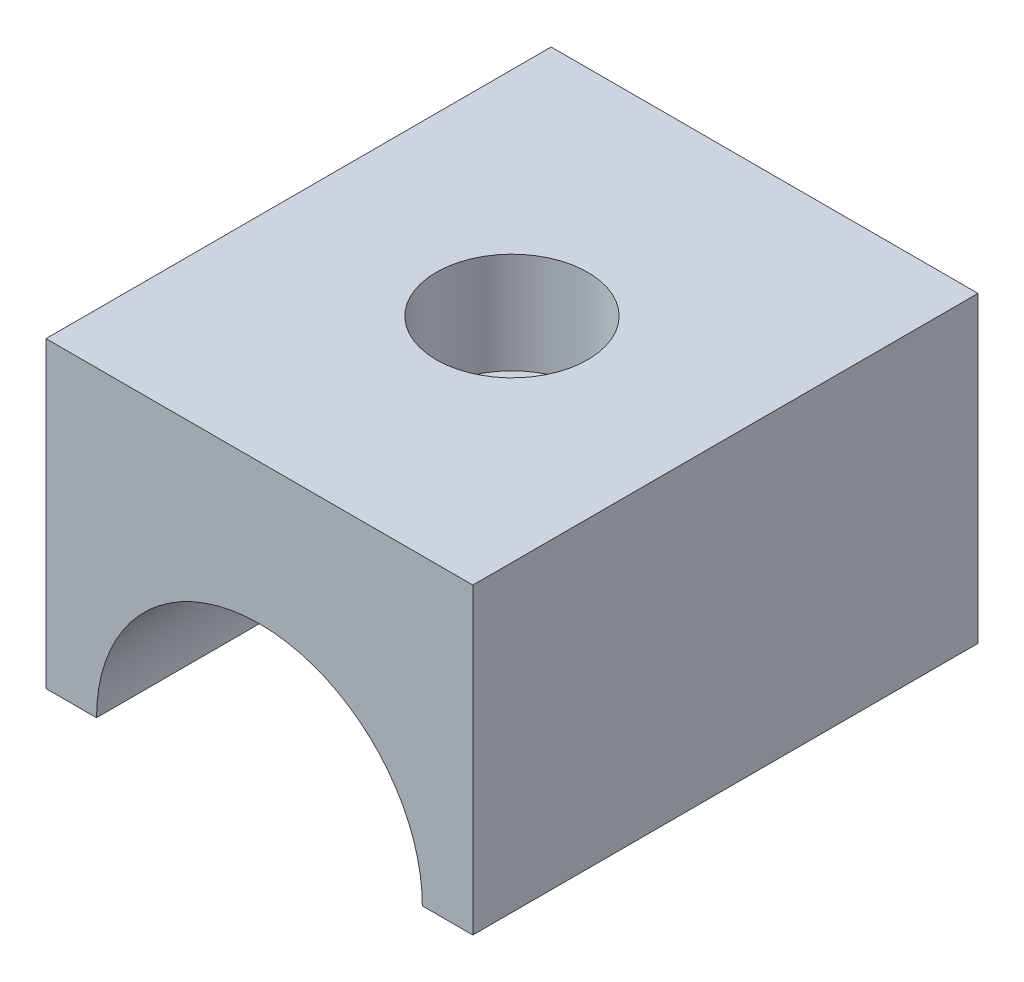
SolidWorks part; units mm, degrees
ref_plane "Front Plane" through (0, 0, 0) normal (0, 0, 1) x (1, 0, 0)
ref_plane "Top Plane" through (0, 0, 0) normal (0, 1, 0) x (1, 0, 0)
ref_plane "Right Plane" through (0, 0, 0) normal (1, 0, 0) x (0, 0, -1)
sketch "Sketch2" plane through (0, 0, 0) normal (0, 0, 1) x (1, 0, 0)
  line L0 (0, 0) -> (-2, 0)
  line L1 (-2, 0) -> (-2, 12)
  line L2 (-2, 12) -> (14.9, 12)
  line L3 (14.9, 12) -> (14.9, 0)
  line L4 (14.9, 0) -> (12.9, 0)
  arc A0 (0, 0) -> (12.9, 0) centre (6.45, 0) cw
  dimension "D1" = 6.45
  dimension "D2" = 2
  dimension "D3" = 2
  dimension "D4" = 12
extrude "Boss-Extrude1" add sketch "Sketch2" against normal blind 20
ref_plane "Plane1" through (0, 12, 0) normal (0, 1, 0) x (1, 0, 0)
sketch "Sketch3" plane through (0, 12, 0) normal (0, 1, 0) x (1, 0, 0)
  line L0 (14.9, 0) -> (-2, 0) construction
  line L1 (-2, 20) -> (-2, 0) construction
  circle A0 centre (6.45, 10) radius 1.6
  point P5 (6.45, 0)
  point P11 (-2, 10)
  dimension "D1" = 3.2
extrude "Cut-Extrude1" cut sketch "Sketch3" against normal blind 20
sketch "Sketch4" plane through (0, 12, 0) normal (0, 1, 0) x (1, 0, 0)
  circle A0 centre (6.45, 10) radius 3
extrude "Cut-Extrude2" cut sketch "Sketch4" against normal blind 4
